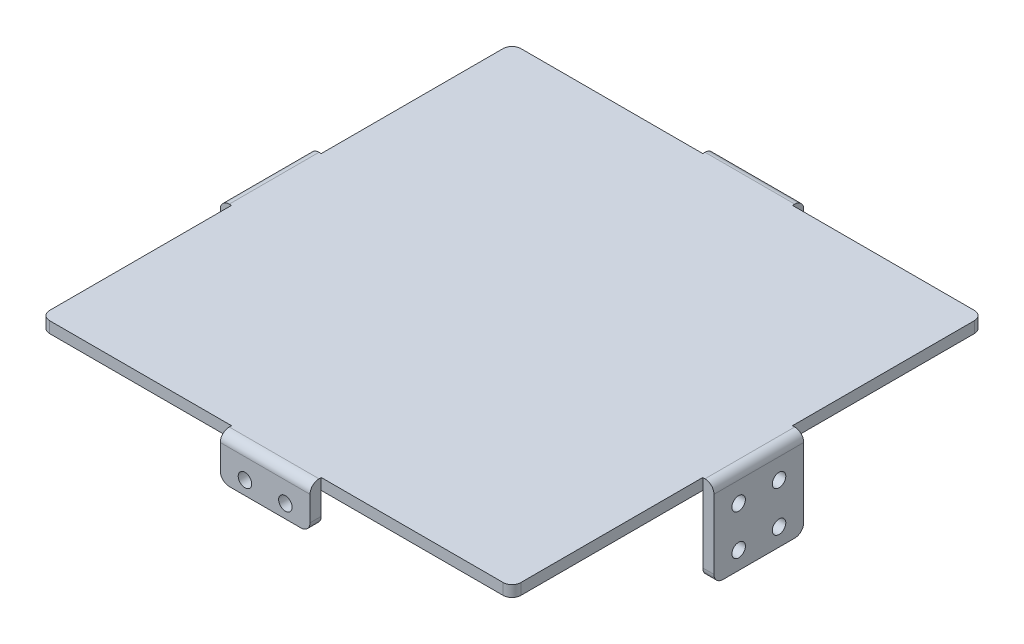
SolidWorks part; units mm, degrees
ref_plane "Front Plane" through (0, 0, 0) normal (0, 0, 1) x (1, 0, 0)
ref_plane "Top Plane" through (0, 0, 0) normal (0, 1, 0) x (1, 0, 0)
ref_plane "Right Plane" through (0, 0, 0) normal (1, 0, 0) x (0, 0, -1)
sketch "Sketch1" plane through (0, 0, 0) normal (0, 1, 0) x (1, 0, 0)
  line L1 (-52.5, -52.5) -> (52.5, -52.5)
  line L2 (-52.5, -52.5) -> (-52.5, 52.5)
  line L3 (-52.5, 52.5) -> (52.5, 52.5)
  line L4 (52.5, -52.5) -> (52.5, 52.5)
  line L5 (-52.5, -52.5) -> (52.5, 52.5) construction
  line L6 (-52.5, 52.5) -> (52.5, -52.5) construction
  point P0 (0, 0)
  dimension "D1" = 105
extrude "Boss-Extrude1" add sketch "Sketch1" along normal blind 2.5 contours L2 L1 L4 L3
sketch "Sketch2" plane through (0, 2.5, 0) normal (0, 1, 0) x (1, 0, 0)
  line L0 (-52.5, 52.5) -> (52.5, 52.5) construction
  line L1 (-10, 52.5) -> (10, 52.5)
  line L2 (-10, 52.5) -> (-10, 55)
  line L3 (-10, 55) -> (10, 55)
  line L4 (10, 52.5) -> (10, 55)
  line L5 (-52.5, -52.5) -> (-52.5, 52.5) construction
  line L6 (-52.5, 0) -> (52.5, 0) construction
  line L7 (52.5, -52.5) -> (52.5, 52.5) construction
  line L8 (-10, -55) -> (10, -55)
  line L9 (10, -52.5) -> (10, -55)
  line L10 (-10, -52.5) -> (10, -52.5)
  line L11 (-10, -52.5) -> (-10, -55)
  point P13 (0, 0)
  point P17 (-52.5, 0)
  dimension "D1" = 20
  dimension "D2" = 42.5
  dimension "D3" = 2.5
sketch "Sketch3" plane through (0, 2.5, 0) normal (0, 1, 0) x (1, 0, 0)
  line L0 (0, 52.5) -> (0, -52.5) construction
  line L1 (-10, 52.5) -> (10, 52.5) construction
  line L2 (-10, -52.5) -> (10, -52.5) construction
  line L3 (52.5, -52.5) -> (52.5, 52.5) construction
  line L4 (52.5, -10) -> (55, -10)
  line L5 (52.5, -10) -> (52.5, 10)
  line L6 (52.5, 10) -> (55, 10)
  line L7 (55, -10) -> (55, 10)
  line L8 (-52.5, 52.5) -> (52.5, 52.5) construction
  line L9 (-52.5, 10) -> (-55, 10)
  line L10 (-55, -10) -> (-55, 10)
  line L11 (-52.5, -10) -> (-55, -10)
  line L12 (-52.5, -10) -> (-52.5, 10)
  dimension "D1" = 20
  dimension "D2" = 42.5
  dimension "D3" = 2.5
extrude "Boss-Extrude2" add sketch "Sketch2" against normal blind 9.5
extrude "Boss-Extrude3" add sketch "Sketch3" against normal blind 19.45
sketch "Sketch4" plane through (0, 0, 55) normal (0, 0, 1) x (1, 0, 0)
  line L0 (0, 2.5) -> (0, -7) construction
  line L1 (-10, 2.5) -> (10, 2.5) construction
  line L2 (-10, -7) -> (10, -7) construction
  line L3 (-52.5, 0) -> (-10, 0) construction
  circle A0 centre (-4.5, -4) radius 1.5
  circle A1 centre (4.5, -4) radius 1.5
  dimension "D1" = 3
  dimension "D2" = 4.5
  dimension "D3" = 4
extrude "Cut-Extrude1" cut sketch "Sketch4" against normal through all
sketch "Sketch5" plane through (55, 0, 0) normal (1, 0, 0) x (0, 0, -1)
  line L1 (-10, -16.95) -> (-10, 2.5) construction
  line L2 (0, 2.5) -> (0, -16.95) construction
  line L3 (-10, 2.5) -> (10, 2.5) construction
  line L4 (-10, -16.95) -> (10, -16.95) construction
  line L5 (10, -8.5) -> (-10, -8.5) construction
  line L6 (10, -16.95) -> (10, 2.5) construction
  circle A0 centre (-4.5, -4) radius 1.5
  circle A1 centre (4.5, -4) radius 1.5
  circle A2 centre (4.5, -13) radius 1.5
  circle A3 centre (-4.5, -13) radius 1.5
  dimension "D1" = 3
  dimension "D2" = 4.5
  dimension "D3" = 4.5
  dimension "D4" = 8.45
extrude "Cut-Extrude2" cut sketch "Sketch5" against normal through all
fillet "Fillet1" radius 2 8 edges at (-10, -7, -53.75) (10, -7, -53.75) (10, -7, 53.75) (-10, -7, 53.75) (53.75, -16.95, 10) (53.75, -16.95, -10) (-53.75, -16.95, -10) (-53.75, -16.95, 10)
fillet "Fillet2" radius 2 4 edges at (-55, 2.5, 0) (55, 2.5, 0) (0, 2.5, -55) (0, 2.5, 55)
fillet "Fillet3" radius 2 4 edges at (52.5, 1.25, -52.5) (52.5, 1.25, 52.5) (-52.5, 1.25, 52.5) (-52.5, 1.25, -52.5)
